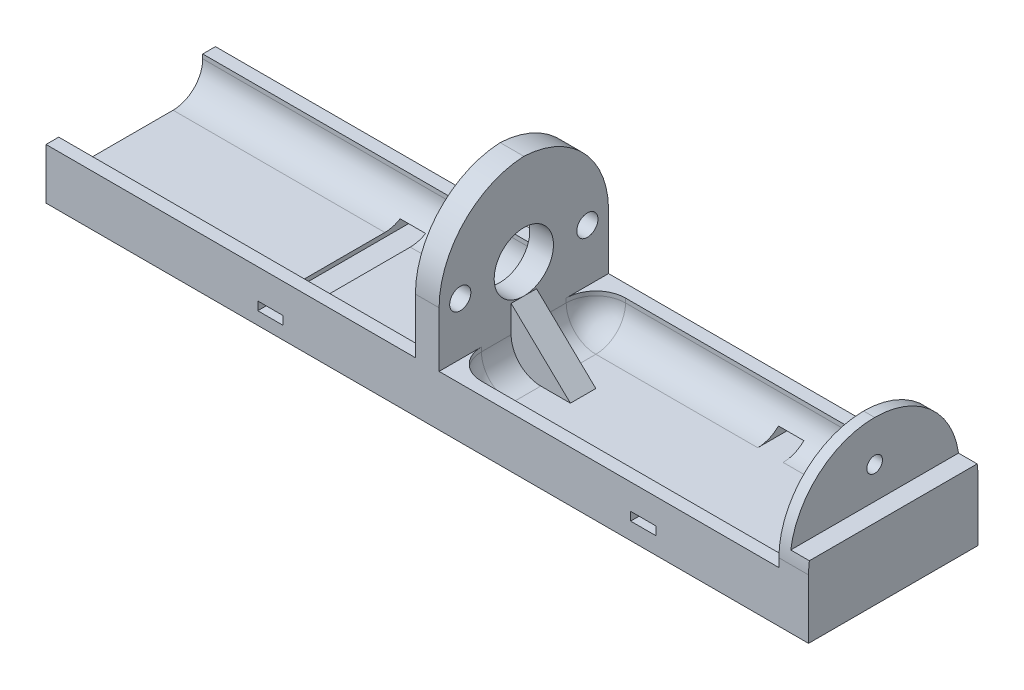
SolidWorks part; units mm, degrees
ref_plane "Front Plane" through (0, 0, 0) normal (0, 0, 1) x (1, 0, 0)
ref_plane "Top Plane" through (0, 0, 0) normal (0, 1, 0) x (1, 0, 0)
ref_plane "Right Plane" through (0, 0, 0) normal (1, 0, 0) x (0, 0, -1)
sketch "Sketch1" plane through (0, 0, 0) normal (1, 0, 0) x (0, 0, -1)
  line L1 (0, 0) -> (20, 0)
  line L2 (0, 0) -> (0, 2)
  line L3 (0, 2) -> (20, 2)
  line L4 (20, 0) -> (20, 2)
  dimension "D1" = 20
  dimension "D2" = 2
extrude "Boss-Extrude1" add sketch "Sketch1" along normal blind 90
sketch "Sketch2" plane through (0, 2, 0) normal (0, 1, 0) x (1, 0, 0)
  line L0 (90, 20) -> (0, 20) construction
  line L1 (43.6, 20) -> (46.3955, 20)
  line L2 (43.6, 20) -> (43.6, 0)
  line L3 (43.6, 0) -> (46.3955, 0)
  line L4 (46.3955, 20) -> (46.3955, 0)
  line L5 (90, 0) -> (0, 0) construction
  line L6 (0, 20) -> (0, 0) construction
  dimension "D1" = 43.6
  dimension "D2" = 2.7955
extrude "Boss-Extrude2" add sketch "Sketch2" along normal blind 21
sketch "Sketch3" plane through (0, 2, 0) normal (0, 1, 0) x (1, 0, 0)
  line L0 (90, 0) -> (46.3955, 0) construction
  line L1 (90, 20) -> (86.5, 20)
  line L2 (90, 20) -> (90, 0)
  line L3 (90, 0) -> (86.5, 0)
  line L4 (86.5, 20) -> (86.5, 0)
  dimension "D1" = 3.5
extrude "Boss-Extrude3" add sketch "Sketch3" along normal blind 15
fillet "Fillet1" radius 10.5 2 edges at (44.9977, 23, 0) (44.9977, 23, -20)
fillet "Fillet2" radius 10 2 edges at (88.25, 17, -20) (88.25, 17, 0)
sketch "Sketch4" plane through (86.5, 0, 0) normal (-1, 0, 0) x (0, 0, 1)
  line L1 (0, 2) -> (-1.5, 2)
  line L2 (0, 2) -> (0, 6)
  line L3 (0, 6) -> (-1.5, 6)
  line L4 (-1.5, 2) -> (-1.5, 6)
  line L5 (-20, 2) -> (-18.5, 2)
  line L6 (-20, 2) -> (-20, 6)
  line L7 (-20, 6) -> (-18.5, 6)
  line L8 (-18.5, 2) -> (-18.5, 6)
  dimension "D1" = 1.5
  dimension "D2" = 4
extrude "Boss-Extrude4" add sketch "Sketch4" along normal up to surface (86.5 mm away) up to face at (0, 1, -10)
sketch "Sketch5" plane through (43.6, 0, 0) normal (-1, 0, 0) x (0, 0, 1)
  line L0 (-10, 2) -> (-10, 24.0025) construction
  line L1 (-18.5, 2) -> (-1.5, 2) construction
  line L2 (-10, 12.2) -> (-24.4443, 12.2) construction
  circle A0 centre (-10, 12.2) radius 7.5 construction
  circle A1 centre (-10, 12.2) radius 10.2 construction
  circle A2 centre (-17.5, 12.2) radius 1.25
  circle A3 centre (-2.5, 12.2) radius 1.25
  circle A4 centre (-10, 12.2) radius 3.5
  point P17 (-10, 12.2)
  dimension "D1" = 15
  dimension "D2" = 20.4
  dimension "D3" = 2.5
  dimension "D4" = 2
  dimension "D5" = 7
extrude "Cut-Extrude1" cut sketch "Sketch5" against normal up to next
sketch "Sketch6" plane through (86.5, 0, 0) normal (-1, 0, 0) x (0, 0, 1)
  circle A0 centre (-10, 12.2) radius 0.925
  circle A1 centre (-10, 12.2) radius 3.5 construction
  dimension "D1" = 1.85
extrude "Cut-Extrude2" cut sketch "Sketch6" against normal up to next
sketch "Sketch7" plane through (90, 0, 0) normal (1, 0, 0) x (0, 0, -1)
  line L1 (0, 8.4) -> (20, 8.4)
  line L2 (0, 8.4) -> (0, 17)
  line L3 (0, 17) -> (20, 17)
  line L4 (20, 8.4) -> (20, 17)
  line L5 (20, 12.5) -> (20, 6) construction
  line L7 (0, 0) -> (20, 0) construction
  arc A0 (20, 7) -> (10, 17) centre (10, 7) ccw construction
  dimension "D1" = 8.4
extrude "Cut-Extrude3" cut sketch "Sketch7" against normal blind 2.2
fillet "Fillet3" radius 3.5 4 edges at (21.8, 2, -1.5) (66.4477, 2, -1.5) (66.4477, 2, -18.5) (21.8, 2, -18.5)
fillet "Fillet4" radius 3.5 5 edges at (46.3955, 5.75, -1.5) (46.3955, 5.75, -18.5) (46.3955, 3.0251, -17.4749) (46.3955, 3.0251, -2.5251)
sketch "Sketch8" plane through (0, 0, -20) normal (0, 0, -1) x (-1, 0, 0)
  line L1 (-27.995, 1.5) -> (-24.995, 1.5)
  line L2 (-27.995, 1.5) -> (-27.995, 2.5)
  line L3 (-27.995, 2.5) -> (-24.995, 2.5)
  line L4 (-24.995, 1.5) -> (-24.995, 2.5)
  line L5 (-90, 0) -> (0, 0) construction
  line L6 (-86.5, 2) -> (-49.8955, 2) construction
  line L7 (-72, 2) -> (-69, 2)
  line L8 (-72, 2) -> (-72, 3)
  line L9 (-72, 3) -> (-69, 3)
  line L10 (-69, 2) -> (-69, 3)
  line L11 (-90, 0) -> (-90, 7) construction
  dimension "D1" = 3
  dimension "D2" = 1
  dimension "D3" = 25
  dimension "D4" = 1.5
  dimension "D5" = 1
  dimension "D6" = 3
  dimension "D7" = 18
extrude "zipTieHole" cut sketch "Sketch8" against normal through all
ref_plane "Plane2" through (46.3955, 5.5, -10) normal (0, 0, 1) x (1, 0, 0)
sketch "Sketch10" plane through (46.3955, 5.5, -10) normal (0, 0, 1) x (1, 0, 0)
  line L0 (7, -3.5) -> (0, 3.2)
  line L2 (0, 3.2) -> (0, -3.5)
  line L3 (-2.7955, -3.5) -> (-18.4005, -3.5) construction
  line L4 (0, -3.5) -> (7, -3.5)
  dimension "D1" = 7
extrude "Boss-Extrude5" add sketch "Sketch10" along normal blind 1.5 and the other way blind 1.5
